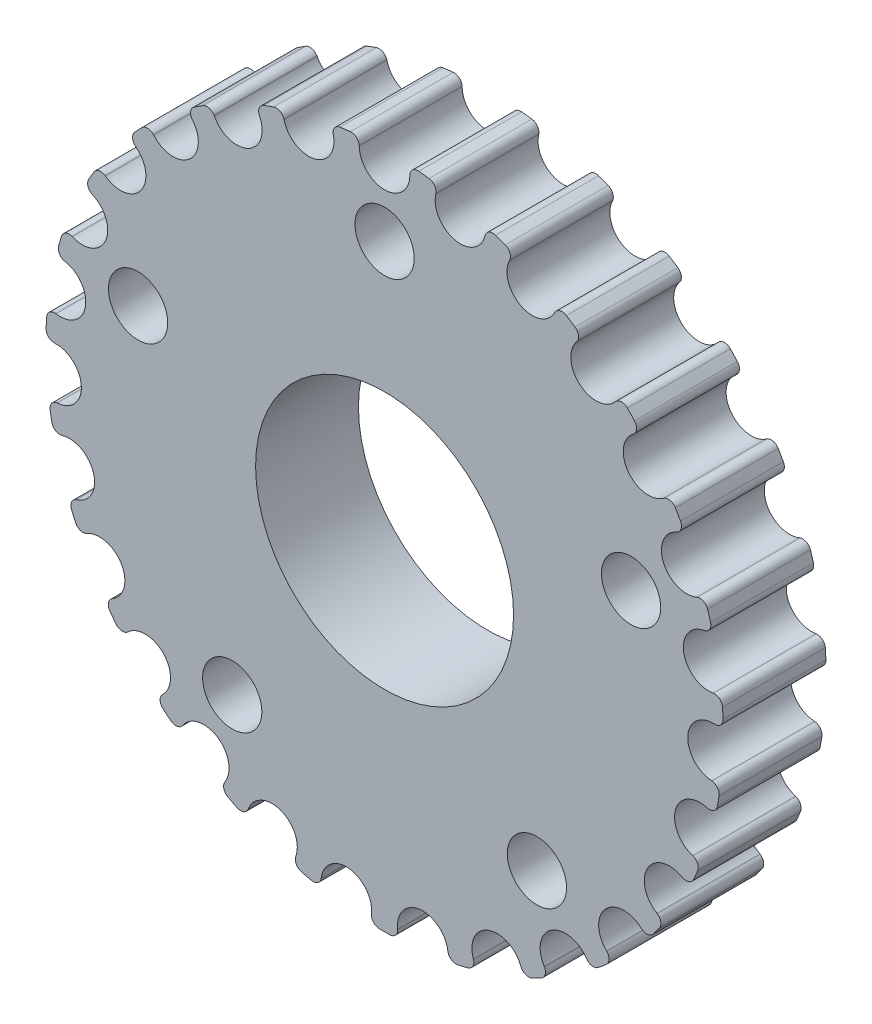
SolidWorks part; units mm, degrees
material "6061-T6 (SS)"
ref_plane "Front Plane" through (0, 0, 0) normal (0, 0, 1) x (1, 0, 0)
ref_plane "Top Plane" through (0, 0, 0) normal (0, 1, 0) x (1, 0, 0)
ref_plane "Right Plane" through (0, 0, 0) normal (1, 0, 0) x (0, 0, -1)
sketch "Pitch diameter" plane through (0, 0, 0) normal (0, 0, 1) x (1, 0, 0)
  circle A0 centre (0, 0) radius 21.4859 construction
  dimension "D1" = 42.9718
sketch "Sketch2" plane through (0, 0, 0) normal (0, 0, 1) x (1, 0, 0)
  circle A0 centre (0, 0) radius 20.9144
  dimension "D1" = 41.8288
extrude "Boss-Extrude1" add sketch "Sketch2" along normal blind 6.35
sketch "Sketch3" plane through (0, 0, 0) normal (0, 0, -1) x (-1, 0, 0)
  line L0 (-1.6014, 20.853) -> (-1.56, 20.3144)
  line L1 (1.6014, 20.853) -> (1.56, 20.3144)
  line L2 (-1.56, 20.3144) -> (1.56, 20.3144) construction
  circle A0 centre (0, 0) radius 20.9144 construction
  arc A1 (-1.56, 20.3144) -> (1.56, 20.3144) centre (0, 20.3144) ccw
  circle A2 centre (0, 0) radius 20.9144 construction
  arc A3 (1.6014, 20.853) -> (-1.6014, 20.853) centre (0, 0) ccw
  point P10 (0, 20.3144)
  point P15 (0, 18.7544)
  point P16 (0, 20.9144)
  dimension "D1" = 1.56
  dimension "D2" = 2.16
extrude "Cut-Extrude1" cut sketch "Sketch3" against normal through all
fillet "Fillet1" radius 0.5 2 edges at (-1.6014, 20.853, 3.175) (1.6014, 20.853, 3.175)
pattern_circular "CirPattern1" count 27 over 360 about axis through (0, 0, 0) along (0, 0, 1) of "Cut-Extrude1", "Fillet1"
sketch "Sketch4" plane through (0, 0, 6.35) normal (0, 0, 1) x (1, 0, 0)
  circle A0 centre (0, 0) radius 7.9629
  dimension "D1" = 15.9258
extrude "Cut-Extrude2" cut sketch "Sketch4" against normal through all
sketch "Sketch5" plane through (0, 0, 6.35) normal (0, 0, 1) x (1, 0, 0)
  line L0 (0, 0) -> (0, 16)
  point P0 (0, 0)
  point P7 (0, 0)
  dimension "D1" = 16
sketch "Sketch9" plane through (0, 0, 6.35) normal (0, 0, 1) x (1, 0, 0)
  point P0 (0, 16)
hole_wizard "#6 Clearance Hole1" positions "Sketch9" profile "Sketch10" hole size "#6" standard "ANSI Inch" end condition through all
sketch "Sketch10" plane through (0, 16, 6.35) normal (1, 0, 0) x (0, -1, 0)
  line L0 (0, 0) -> (0, 6.35)
  line L1 (0, 6.35) -> (1.8288, 6.35)
  line L2 (1.8288, 6.35) -> (1.8288, 0)
  line L5 (1.8288, 0) -> (0, 0)
  line L11 (0, -6.35) -> (0, 107.95) construction
  dimension "Thru Hole Dia." = 3.6576
  dimension "Thru Hole Depth" = 6.35
pattern_circular "CirPattern2" count 5 over 360 about axis through (0, 0, 6.35) along (0, 0, 1) of "#6 Clearance Hole1"
sketch "Sketch11" plane through (0, 0, 0) normal (0, 0, -1) x (-1, 0, 0)
  circle A0 centre (0, 0) radius 12.5
  dimension "D1" = 25
extrude "Cut-Extrude3" [suppressed] cut sketch "Sketch11" against normal through all
equation "\"NumberOfTeeth\"= 27"
equation "\"Pitch\"= 5mm"
equation "\"PitchDiameter\"= ( \"Pitch\" * \"NumberOfTeeth\" ) / Pi"
equation "\"OD\"= \"PitchDiameter\" - 0.0225in * 2"
equation "\"D1@Pitch diameter\" = \"PitchDiameter\""
equation "\"D1@Sketch2\"=\"OD\""
equation "\"D1@CirPattern1\"=\"NumberOfTeeth\""
